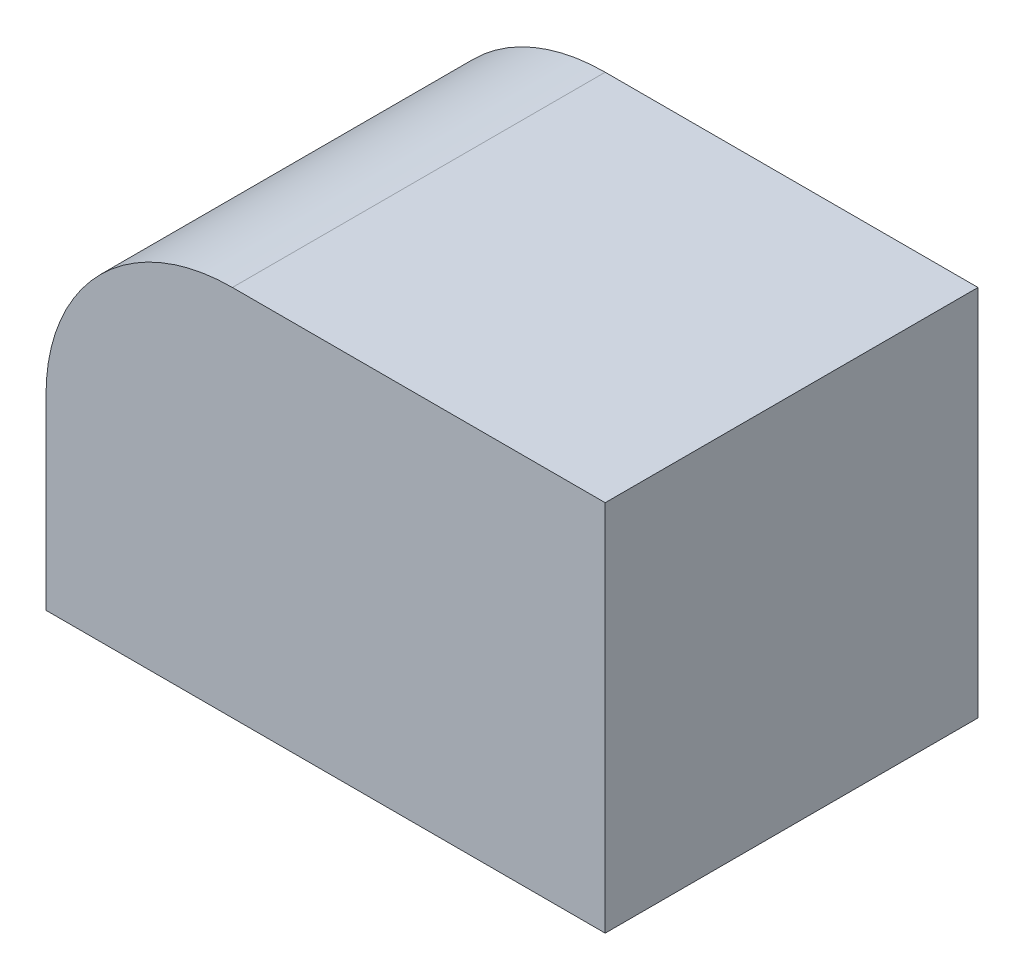
SolidWorks part; units mm, degrees
material "炭素鋼(普通)"
ref_plane "VERT" through (0, 0, 0) normal (0, 0, 1) x (1, 0, 0)
ref_plane "HOR" through (0, 0, 0) normal (0, 1, 0) x (1, 0, 0)
ref_plane "CTR" through (0, 0, 0) normal (1, 0, 0) x (0, 0, -1)
ref_axis "A_X" through (33, 0, 0) along (-1, 0, 0)
ref_axis "A_Y" through (0, 42, 0) along (0, -1, 0)
ref_axis "A_Z" through (0, 0, 22) along (0, 0, -1)
sketch3d "PNT_CG"
  point P0 (0, 0, 0)
sketch "Sketch1" plane through (0, 0, 0) normal (0, 1, 0) x (1, 0, 0)
  line L1 (30, -20) -> (-30, -20)
  line L2 (30, -20) -> (30, 20)
  line L3 (30, 20) -> (-30, 20)
  line L4 (-30, -20) -> (-30, 20)
  line L5 (30, -20) -> (-30, 20) construction
  line L6 (30, 20) -> (-30, -20) construction
  point P0 (0, 0)
  dimension "D1" = 40
  dimension "D2" = 60
extrude "Boss-Extrude1" add sketch "Sketch1" along normal blind 40
fillet "Fillet1" radius 20 1 edges at (-30, 40, 0)
